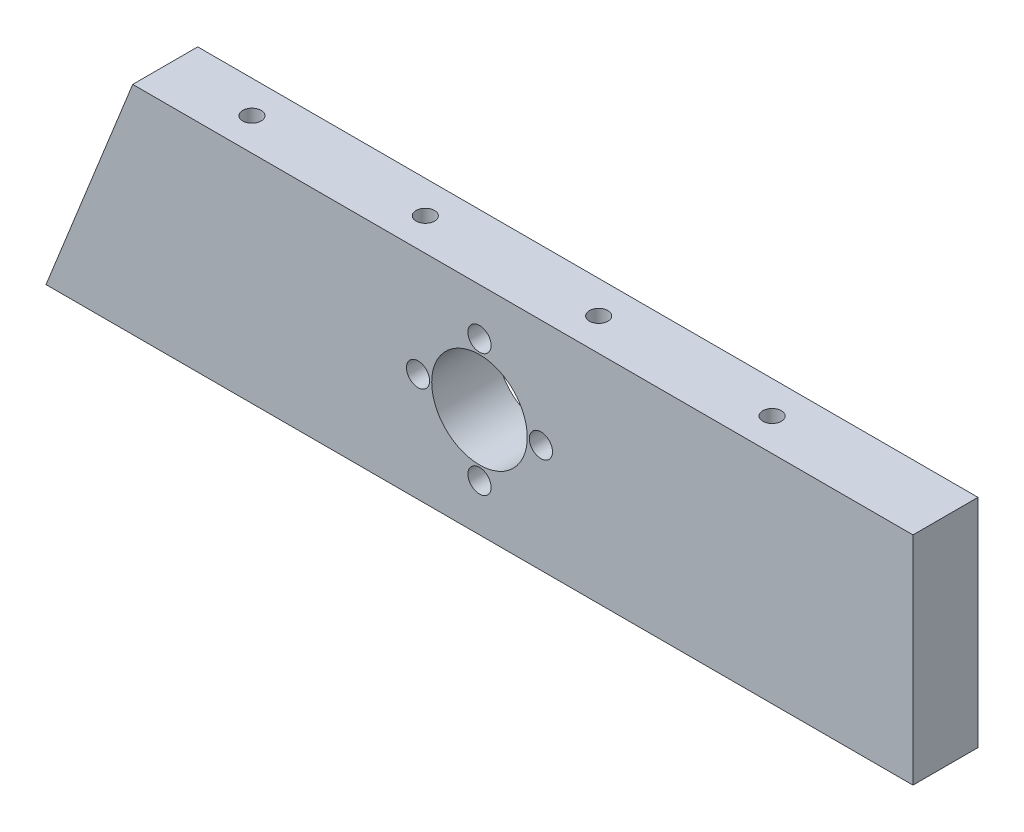
SolidWorks part; units mm, degrees
material "PE High Density Film"
ref_plane "Front Plane" through (0, 0, 0) normal (0, 0, 1) x (1, 0, 0)
ref_plane "Top Plane" through (0, 0, 0) normal (0, 1, 0) x (1, 0, 0)
ref_plane "Right Plane" through (0, 0, 0) normal (1, 0, 0) x (0, 0, -1)
sketch "Sketch1" plane through (0, 0, 0) normal (0, 0, 1) x (1, 0, 0)
  line L1 (-50.8, 15.875) -> (63.5, 15.875)
  line L2 (-50.8, 15.875) -> (-63.5, -15.875)
  line L3 (-63.5, -15.875) -> (63.5, -15.875)
  line L4 (63.5, 15.875) -> (63.5, -15.875)
  circle A0 centre (0, -9) radius 1.7
  circle A1 centre (-9, 0) radius 1.7
  circle A2 centre (0, 9) radius 1.7
  circle A3 centre (9, 0) radius 1.7
  arc A8 (-5.3578, -2.967) -> (-5.3172, -2.9531) centre (-6.35, 0) ccw construction
  circle A16 centre (0, 0) radius 7
  circle A17 centre (0, 0) radius 9 construction
  point P0 (0, 0)
  dimension "D3" = 3.4
  dimension "D5" = 14
  dimension "D1" = 127
  dimension "D2" = 31.75
  dimension "D8" = 114.3
  dimension "D11" = 9
  dimension "D4" = 63.5
extrude "Boss-Extrude1" add sketch "Sketch1" along normal blind 9.525
hole_wizard "Tap Drill for #6-32 Tap1" positions "Sketch11" profile "Sketch12" hole size "#6-32" standard "ANSI Inch"
sketch "Sketch11" plane through (0, -15.875, 0) normal (0, -1, 0) x (-1, 0, 0)
  line L0 (-63.5, -9.525) -> (-63.5, 0) construction
  line L1 (63.5, -9.525) -> (-63.5, -9.525) construction
  point P0 (-38.1, -4.7625)
  dimension "D1" = 25.4
  dimension "D2" = 4.7625
sketch "Sketch12" plane through (38.1, -15.875, 4.7625) normal (1, 0, 0) x (0, 0, -1)
  line L0 (0, 0) -> (0, 13.5127)
  line L1 (0, 13.5127) -> (1.3525, 12.7)
  line L2 (1.3525, 12.7) -> (1.3525, 0)
  line L5 (1.3525, 0) -> (0, 0)
  line L10 (0, 13.5127) -> (-1.3526, 12.7) construction
  line L11 (0, -6.35) -> (0, 107.95) construction
  dimension "Hole Dia." = 2.7051
  dimension "Hole Depth" = 12.7
  dimension "Drill Angle" = 118
pattern_linear "LPattern1" count 4 spacing 25.4 along (-1, 0, 0) of "Tap Drill for #6-32 Tap1"
mirror "Mirror8" about plane through (0, 0, 0) normal (0, 1, 0) of "Tap Drill for #6-32 Tap1", "LPattern1"
equation "\"Plate Screw Hole Diameter\"= 0.116in"
equation "\"Plate Width\" = 5in"
equation "\"Plate Thickness\" = 0.375in"
equation "\"Num holes\" = 4"
equation "\"Plate Height\" = 1.25in"
equation "\"D1@Sketch11\"=\"Plate Width\" / ( \"Num holes\" + 1)"
equation "\"D2@Sketch11\"=\"Plate Thickness\"/2"
equation "\"D3@LPattern1\"=\"Plate Width\" / ( \"Num holes\"  + 1 )"
equation "\"D1@Sketch1\"=\"Plate Width\""
equation "\"D2@Sketch1\"=\"Plate Height\""
equation "\"D4@Sketch1\"= \"Plate Width\"/2"
equation "\"Top Plate WIdth\" = 4.5in"
equation "\"D8@Sketch1\"=\"Top Plate Width\""
